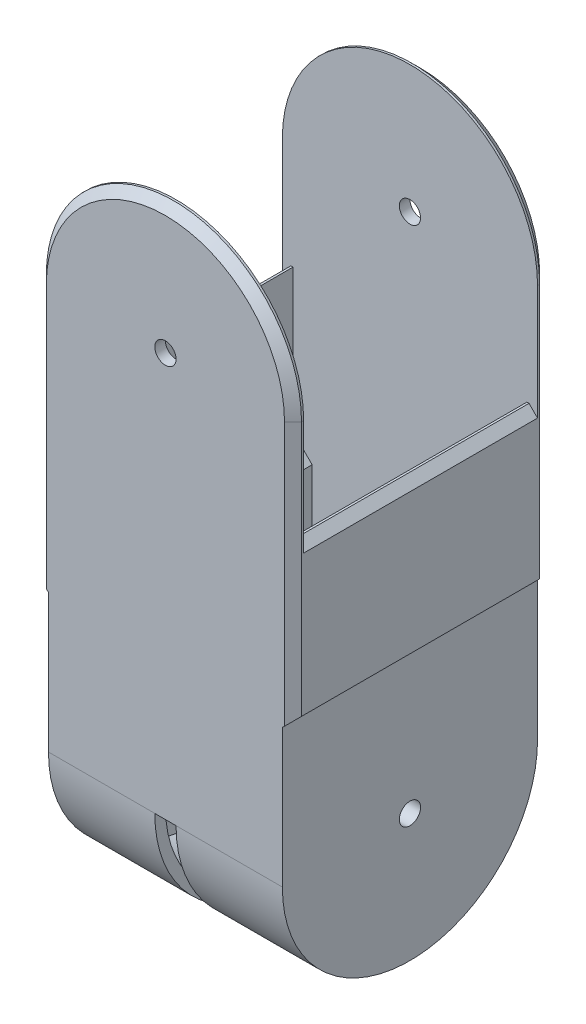
SolidWorks part; units mm, degrees
ref_plane "Front Plane" through (0, 0, 0) normal (0, 0, 1) x (1, 0, 0)
ref_plane "Top Plane" through (0, 0, 0) normal (0, 1, 0) x (1, 0, 0)
ref_plane "Right Plane" through (0, 0, 0) normal (1, 0, 0) x (0, 0, -1)
sketch "Sketch1" plane through (0, 0, 0) normal (0, 1, 0) x (1, 0, 0)
  line L1 (-30, -30) -> (30, -30)
  line L2 (-30, -30) -> (-30, 30)
  line L3 (-30, 30) -> (30, 30)
  line L4 (30, -30) -> (30, 30)
  line L5 (-30, -30) -> (30, 30) construction
  line L6 (-30, 30) -> (30, -30) construction
  point P0 (0, 0)
  dimension "D1" = 60
  dimension "D2" = 60
extrude "Boss-Extrude1" add sketch "Sketch1" along normal blind 100
sketch "Sketch4" plane through (0, 0, -30) normal (0, 0, -1) x (-1, 0, 0)
  line L0 (30, 100) -> (30, 0) construction
  line L1 (-30, 100) -> (30, 100)
  line L2 (-30, 100) -> (-30, 125)
  line L4 (30, 100) -> (30, 125)
  arc A0 (-30, 125) -> (30, 125) centre (0, 125) cw
  circle A1 centre (0, 125) radius 2.5
  dimension "D2" = 5
  dimension "D1" = 25
extrude "Boss-Extrude2" add sketch "Sketch4" against normal blind 2.5
mirror "Mirror2" about plane through (0, 0, 0) normal (0, 0, 1) of "Boss-Extrude2"
sketch "Sketch5" plane through (30, 0, 0) normal (-1, 0, 0) x (0, 0, 1)
  line L0 (0, -33) -> (0, 33) construction
  line L1 (33, 0) -> (-33, 0) construction
  line L2 (-30, 125) -> (-30, 0) construction
  line L3 (30, 30) -> (30, 0)
  line L4 (30, 0) -> (-30, 0)
  line L5 (-30, 0) -> (-30, 30)
  arc A0 (-30, 30) -> (30, 30) centre (0, 30) ccw
  circle A1 centre (0, 30) radius 2.5
  point P15 (0, 0)
  line M6 (30, 0) -> (-30, 0)
  line M7 (-30, 0) -> (-30, 125)
  line M13 (30, 125) -> (30, 0)
  dimension "D1" = 5
extrude "Cut-Extrude1" cut sketch "Sketch5" along normal through all both and the other way through all contours A0 L4 M7 | A0 M6 M13 | A1 region at (30, 6.701, -23.299) region at (30, 6.701, 23.299)
sketch "Sketch6" plane through (30, 0, 0) normal (1, 0, 0) x (0, 0, -1)
  line L0 (-30, 60) -> (30, 60)
  line L1 (-30, 125) -> (-30, 30) construction
  line L2 (30, 125) -> (30, 30) construction
  line L3 (30, 60) -> (30, 0)
  line L4 (33, 0) -> (-33, 0) construction
  line L5 (30, 0) -> (-30, 0)
  line L6 (-30, 0) -> (-30, 60)
  circle A0 centre (0, 30) radius 30 construction
extrude "Cut-Extrude2" cut sketch "Sketch6" against normal blind 2.5
mirror "Mirror3" about plane through (0, 0, 0) normal (1, 0, 0) of "Cut-Extrude2"
chamfer "Chamfer1" distance 2 angle 45 8 edges at (-30, 100, 0) (30, 100, 0) (-30, 92.5, -30) (30, 92.5, -30) (0, 155, -30) (-30, 92.5, 30) (30, 92.5, 30) (0, 155, 30)
chamfer "Chamfer2" distance 5 angle 45 2 edges at (30, 60, 0) (-30, 60, 0)
sketch "Sketch7" plane through (0, 100, 0) normal (0, 1, 0) x (1, 0, 0)
  line L0 (-30, 27.5) -> (30, 27.5) construction
  line L1 (-27.5, -27.5) -> (27.5, -27.5)
  line L2 (-27.5, -27.5) -> (-27.5, 27.5)
  line L3 (-27.5, 27.5) -> (27.5, 27.5)
  line L4 (27.5, -27.5) -> (27.5, 27.5)
  line L5 (-27.5, -27.5) -> (27.5, 27.5) construction
  line L6 (-27.5, 27.5) -> (27.5, -27.5) construction
  line L7 (30, 27.5) -> (30, -27.5) construction
  point P0 (0, 0)
  dimension "D1" = 2.5
extrude "Cut-Extrude3" cut sketch "Sketch7" against normal up to vertex (35 mm away) up to point (30, 65, 28)
sketch "Sketch8" plane through (0, 65, 0) normal (0, 1, 0) x (1, 0, 0)
  line L0 (-30, 27.5) -> (30, 27.5) construction
  line L1 (-23, -27.5) -> (23, -27.5)
  line L2 (-23, -27.5) -> (-23, 27.5)
  line L3 (-23, 27.5) -> (23, 27.5)
  line L4 (23, -27.5) -> (23, 27.5)
  line L5 (-23, -27.5) -> (23, 27.5) construction
  line L6 (-23, 27.5) -> (23, -27.5) construction
  line L7 (30, 27.5) -> (30, -27.5) construction
  point P0 (0, 0)
  dimension "D1" = 7
extrude "Cut-Extrude4" cut sketch "Sketch8" against normal up to vertex (35 mm away) up to point (27.5, 30, 30)
sketch "Sketch9" plane through (23, 0, 0) normal (-1, 0, 0) x (0, 0, 1)
  line L0 (0, -33) -> (0, 33) construction
  line L1 (-27.5, 30) -> (27.5, 30)
  arc A0 (27.5, 30) -> (-27.5, 30) centre (0, 30) cw
  dimension "D1" = 2.5
  dimension "D2" = 2.5
extrude "Cut-Extrude5" cut sketch "Sketch9" along normal up to surface (46 mm away) up to face at (-23, 42.0833, 0)
sketch "Sketch10" plane through (0, 0, 0) normal (0, 1, 0) x (1, 0, 0)
  line L0 (-27.5, 30) -> (27.5, 30) construction
  line L1 (2.5, 30) -> (-2.5, 30)
  line L2 (2.5, 30) -> (2.5, -30)
  line L3 (2.5, -30) -> (-2.5, -30)
  line L4 (-2.5, 30) -> (-2.5, -30)
  line L5 (2.5, 30) -> (-2.5, -30) construction
  line L6 (2.5, -30) -> (-2.5, 30) construction
  point P0 (0, 0)
  dimension "D1" = 5
extrude "Cut-Extrude6" cut sketch "Sketch10" along normal up to vertex (30 mm away) up to point (27.5, 30, -30)
chamfer "Chamfer3" distance 3 angle 45 2 edges at (-23, 65, 0) (23, 65, 0)
